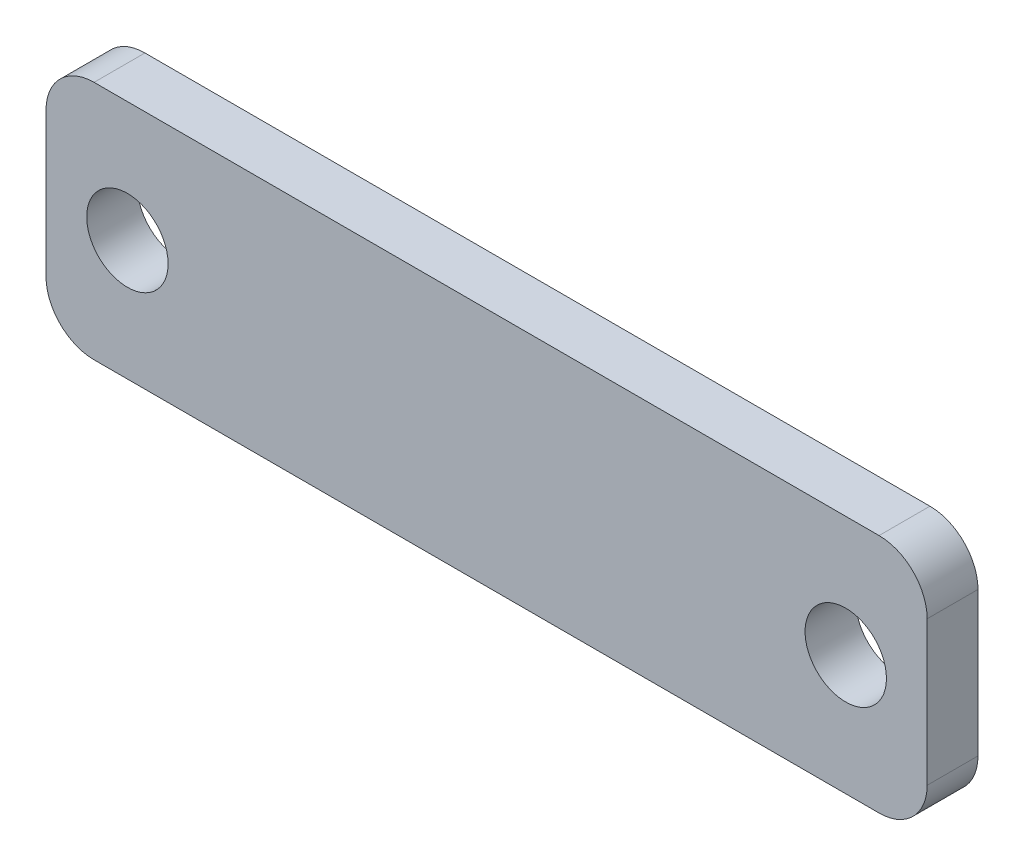
SolidWorks part; units mm, degrees
material "Custom Plastic"
ref_plane "X-Y Datum" through (0, 0, 0) normal (0, 0, 1) x (1, 0, 0)
ref_plane "X-Z Datum" through (0, 0, 0) normal (0, 1, 0) x (1, 0, 0)
ref_plane "Y-Z Datum" through (0, 0, 0) normal (1, 0, 0) x (0, 0, -1)
sketch "Sketch1" plane through (0, 0, 0) normal (0, 0, 1) x (1, 0, 0)
  line L1 (-27.5, -7.5) -> (27.5, -7.5)
  line L2 (-27.5, -7.5) -> (-27.5, 7.5)
  line L3 (-27.5, 7.5) -> (27.5, 7.5)
  line L4 (27.5, -7.5) -> (27.5, 7.5)
  line L5 (-27.5, -7.5) -> (27.5, 7.5) construction
  line L6 (-27.5, 7.5) -> (27.5, -7.5) construction
  point P0 (0, 0)
  dimension "D1" = 15
  dimension "D2" = 55
base flange "Base-Flange1" sketch "Sketch1" thickness 3.175 reverse thickness direction no parameters "D1"=10
sketch "Sketch7" plane through (0, 0, 0) normal (0, 0, 1) x (1, 0, 0)
  line L0 (-27.5, 0) -> (-22.42, 0)
  line L1 (-27.5, 7.5) -> (-27.5, -7.5) construction
  line L2 (0, -43.0151) -> (0, 43.0151) construction
  line L3 (27.5, 0) -> (22.42, 0)
  circle A0 centre (-22.42, 0) radius 2.54
  circle A1 centre (22.42, 0) radius 2.54
  dimension "D1" = 5.08
  dimension "D2" = 5.08
fillet "Fillet1" radius 3 4 edges at (27.5, 7.5, -1.5875) (27.5, -7.5, -1.5875) (-27.5, -7.5, -1.5875) (-27.5, 7.5, -1.5875)
extrude "Cut-Extrude1" cut sketch "Sketch7" against normal through all
sketch "Bend-Lines1" [suppressed] plane through (0, 0, 0) normal (0, 1, 0) x (1, 0, 0)
sketch "Bounding-Box1" [suppressed] plane through (0, 0, 0) normal (0, 1, 0) x (1, 0, 0)
sheet metal parameters "Sheet-Metal1" thickness 3.175 parameters "D1"=10
flat pattern "Flat-Pattern1" [suppressed]
sketch "Bend-Lines2" plane through (0, 0, 0) normal (0, 1, 0) x (1, 0, 0)
sketch3d "Bounding-Box2" [suppressed]
  line L0 (-20, -7.5, 0) -> (20, -7.5, 0) construction
  line L1 (-20, 7.5, 0) -> (20, 7.5, 0) construction
  line L2 (-20, -7.5, 0) -> (-20, 7.5, 0) construction
  line L3 (20, -7.5, 0) -> (20, 7.5, 0) construction
sheet metal parameters "Sheet-Metal2" thickness 3.175 parameters "D1"=10
flat pattern "Flat-Pattern1"
sketch "Bend-Lines2" plane through (0, 0, 0) normal (0, 1, 0) x (1, 0, 0)
sketch3d "Bounding-Box2" [suppressed]
  line L0 (-27.5, -7.5, 0) -> (27.5, -7.5, 0) construction
  line L1 (-27.5, 7.5, 0) -> (27.5, 7.5, 0) construction
  line L2 (-27.5, -7.5, 0) -> (-27.5, 7.5, 0) construction
  line L3 (27.5, -7.5, 0) -> (27.5, 7.5, 0) construction
